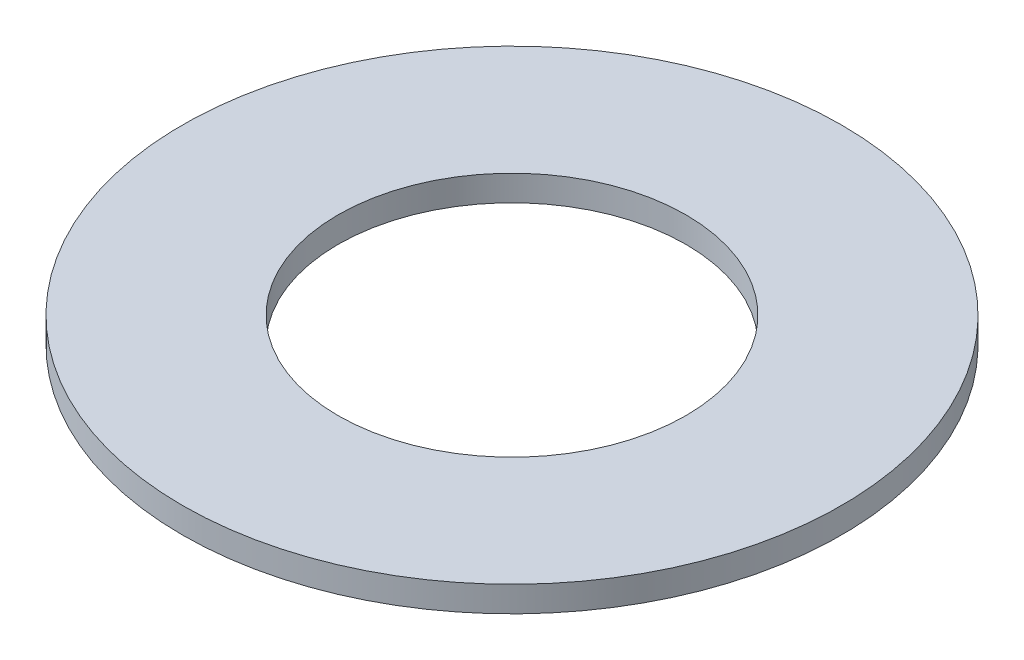
SolidWorks part; units mm, degrees
ref_plane "Front Plane" through (0, 0, 0) normal (0, 0, 1) x (1, 0, 0)
ref_plane "Top Plane" through (0, 0, 0) normal (0, 1, 0) x (1, 0, 0)
ref_plane "Right Plane" through (0, 0, 0) normal (1, 0, 0) x (0, 0, -1)
sketch "Sketch1" plane through (0, 0, 0) normal (0, 1, 0) x (1, 0, 0)
  circle A0 centre (0, 0) radius 90
  dimension "FLANGE_OD" = 180
extrude "Boss-Extrude1" add sketch "Sketch1" along normal blind 7
sketch "Sketch2" plane through (0, 0, 0) normal (0, 1, 0) x (1, 0, 0)
  circle A0 centre (0, 0) radius 47.5
  dimension "BORE_D" = 95
extrude "Cut-Extrude1" cut sketch "Sketch2" along normal through all
sketch "Sketch3" plane through (0, 7, 0) normal (0, 1, 0) x (1, 0, 0)
  circle A0 centre (0, 0) radius 28.1793 construction
  circle A1 centre (-28.1793, 0) radius 5.2519
  dimension "BOLT_D" = 10.5037
  dimension "BOLT_PCD" = 56.3585
extrude "Cut-Extrude2" cut sketch "Sketch3" against normal blind 5.1371 rebuild error yes
pattern_circular "CirPattern1" count 4 over 360 rebuild error yes
